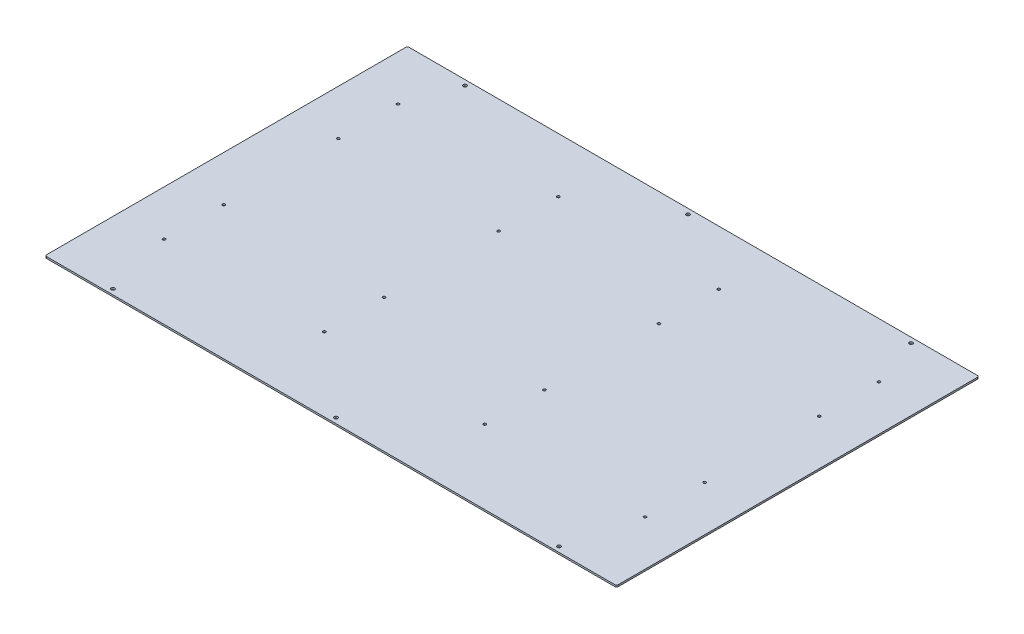
SolidWorks part; units mm, degrees
material "PE High Density"
ref_plane "Front Plane" through (0, 0, 0) normal (0, 0, 1) x (1, 0, 0)
ref_plane "Top Plane" through (0, 0, 0) normal (0, 1, 0) x (1, 0, 0)
ref_plane "Right Plane" through (0, 0, 0) normal (1, 0, 0) x (0, 0, -1)
sketch "Sketch1" plane through (0, 0, 0) normal (0, 1, 0) x (1, 0, 0)
  line L1 (-517.525, -330.2) -> (517.525, -330.2)
  line L2 (-520.7, -327.025) -> (-520.7, 327.025)
  line L3 (-517.525, 330.2) -> (517.525, 330.2)
  line L4 (520.7, -327.025) -> (520.7, 327.025)
  line L5 (-520.7, -330.2) -> (520.7, 330.2) construction
  line L6 (-520.7, 330.2) -> (520.7, -330.2) construction
  arc A0 (-517.525, -330.2) -> (-520.7, -327.025) centre (-517.525, -327.025) cw
  arc A1 (517.525, -330.2) -> (520.7, -327.025) centre (517.525, -327.025) ccw
  arc A2 (517.525, 330.2) -> (520.7, 327.025) centre (517.525, 327.025) cw
  arc A3 (-520.7, 327.025) -> (-517.525, 330.2) centre (-517.525, 327.025) cw
  point P0 (0, 0)
  dimension "D3" = 3.175
  dimension "D1" = 1041.4
  dimension "D2" = 660.4
extrude "Boss-Extrude1" add sketch "Sketch1" along normal blind 3.175
sketch "Sketch2" plane through (0, 3.175, 0) normal (0, 1, 0) x (1, 0, 0)
  line L0 (517.525, 330.2) -> (-517.525, 330.2) construction
  line L1 (-520.7, 327.025) -> (-520.7, -327.025) construction
  line L2 (520.7, -327.025) -> (520.7, 327.025) construction
  line L4 (-517.525, -330.2) -> (517.525, -330.2) construction
  point P0 (-406.4, 320.675)
  point P2 (0, 320.675)
  point P4 (406.4, 320.675)
  point P8 (406.4, -320.675)
  point P10 (0, -320.675)
  point P12 (-406.4, -320.675)
  dimension "D1" = 9.525
  dimension "D2" = 114.3
  dimension "D3" = 406.4
  dimension "D4" = 9.525
  dimension "D5" = 406.4
  dimension "D6" = 114.3
hole_wizard "1/4 (0.25) Diameter Hole1" positions "Sketch3" profile "Sketch4" hole size "1/4" standard "ANSI Inch" end condition through all
sketch "Sketch3" plane through (0, 3.175, 0) normal (0, 1, 0) x (1, 0, 0)
  point P0 (-406.4, 320.675)
  point P6 (0, 320.675)
  point P12 (406.4, 320.675)
  point P24 (406.4, -320.675)
  point P30 (0, -320.675)
  point P36 (-406.4, -320.675)
sketch "Sketch4" plane through (-406.4, 3.175, -320.675) normal (1, 0, 0) x (0, 0, 1)
  line L0 (0, 0) -> (0, 3.175)
  line L1 (0, 3.175) -> (3.175, 3.175)
  line L2 (3.175, 3.175) -> (3.175, 0)
  line L5 (3.175, 0) -> (0, 0)
  line L11 (0, -6.35) -> (0, 107.95) construction
  dimension "Thru Hole Dia." = 6.35
  dimension "Thru Hole Depth" = 3.175
sketch "Sketch5" plane through (0, 3.175, 0) normal (0, 1, 0) x (1, 0, 0)
  point P0 (-438.15, 230.4683)
  point P1 (-438.15, 121.7563)
  point P2 (0, 0)
  point P4 (0, 0)
  point P5 (-146.05, 230.4683)
  point P6 (0, 0)
  point P7 (-146.05, 121.7563)
  point P8 (0, 0)
  point P10 (0, 0)
  point P12 (0, 0)
  point P14 (0, 0)
  point P16 (0, 0)
  point P17 (146.05, 230.4683)
  point P18 (0, 0)
  point P19 (146.05, 121.7563)
  point P20 (0, 0)
  point P22 (0, 0)
  point P23 (438.15, 230.4683)
  point P24 (0, 0)
  point P25 (438.15, 121.7563)
  point P26 (0, 0)
  point P28 (0, 0)
  point P30 (0, 0)
  point P32 (0, 0)
  point P34 (0, 0)
  point P39 (438.15, -87.0317)
  point P43 (438.15, -195.7437)
  point P45 (146.05, -195.7437)
  point P47 (146.05, -87.0317)
  point P51 (-146.05, -87.0317)
  point P55 (-146.05, -195.7437)
  point P63 (-438.15, -87.0317)
  point P65 (-438.15, -195.7437)
  dimension "D1" = 108.712
  dimension "D2" = 108.712
  dimension "D3" = 292.1
  dimension "D4" = 292.1
  dimension "D5" = 146.05
  dimension "D6" = 146.05
  dimension "D7" = 121.7563
  dimension "D8" = 87.0317
hole_wizard "#10 (0.1935) Diameter Hole1" positions "3DSketch1" profile "Sketch6" hole size "#10" standard "ANSI Inch" end condition through all
sketch3d "3DSketch1"
  point P0 (-438.15, 3.175, -230.4683)
  point P6 (-438.15, 3.175, -121.7563)
  point P9 (-146.05, 3.175, -121.7563)
  point P12 (-146.05, 3.175, -230.4683)
  point P24 (146.05, 3.175, -121.7563)
  point P27 (146.05, 3.175, -230.4683)
  point P36 (438.15, 3.175, -230.4683)
  point P39 (438.15, 3.175, -121.7563)
  point P51 (-438.15, 3.175, 87.0317)
  point P54 (-438.15, 3.175, 195.7437)
  point P66 (-146.05, 3.175, 195.7437)
  point P69 (-146.05, 3.175, 87.0317)
  point P75 (146.05, 3.175, 87.0317)
  point P81 (146.05, 3.175, 195.7437)
  point P87 (438.15, 3.175, 87.0317)
  point P90 (438.15, 3.175, 195.7437)
sketch "Sketch6" plane through (-438.15, 3.175, -230.4683) normal (1, 0, 0) x (0, 0, 1)
  line L0 (0, 0) -> (0, 3.175)
  line L1 (0, 3.175) -> (2.4574, 3.175)
  line L2 (2.4574, 3.175) -> (2.4574, 0)
  line L5 (2.4574, 0) -> (0, 0)
  line L11 (0, -6.35) -> (0, 107.95) construction
  dimension "Thru Hole Dia." = 4.9149
  dimension "Thru Hole Depth" = 3.175
